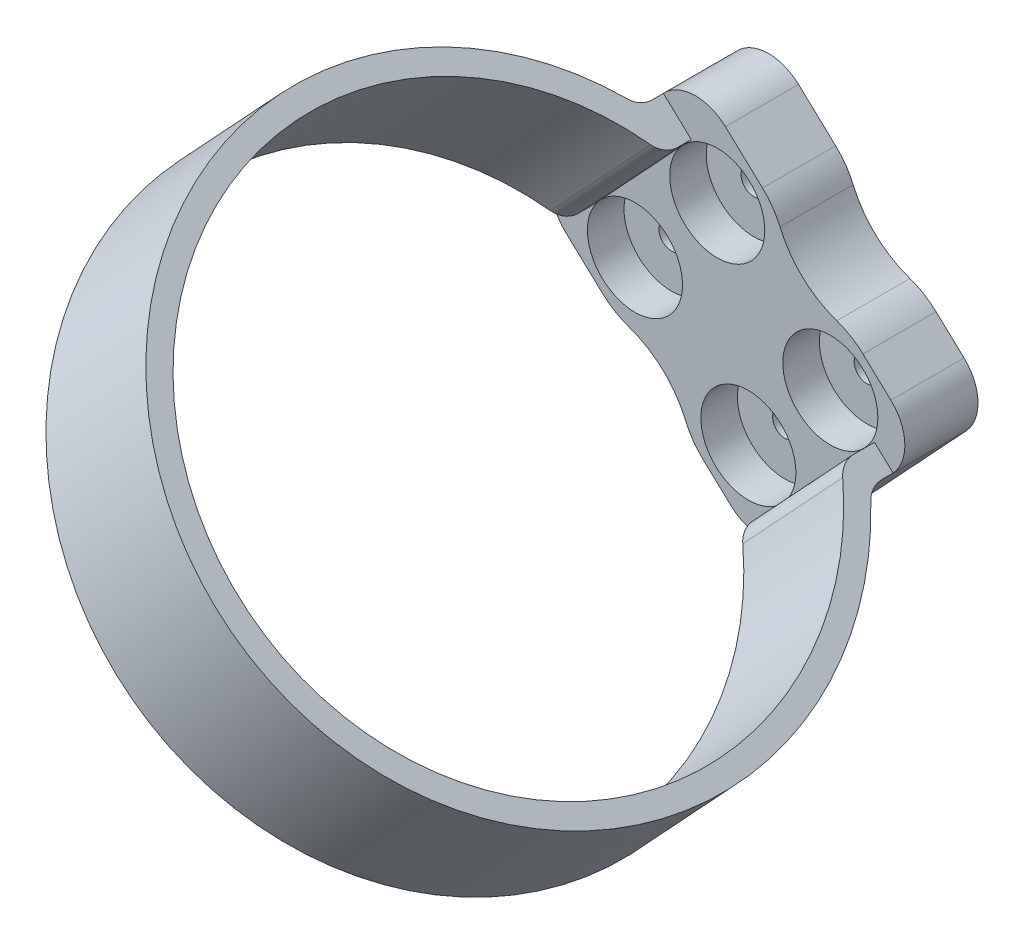
SolidWorks part; units mm, degrees
note: '?' marks a value the reader was unsure of.
ref_plane "Front Plane" through (0, 0, 0) normal (0, 0, 1) x (1, 0, 0)
ref_plane "Top Plane" through (0, 0, 0) normal (0, 1, 0) x (1, 0, 0)
ref_plane "Right Plane" through (0, 0, 0) normal (1, 0, 0) x (0, 0, -1)
sketch "Sketch1" plane through (0, 0, 0) normal (0, 0, 1) x (1, 0, 0)
  line L0 (-3.0751, 21.3626) -> (19.5471, 0.292)
  line L1 (10.5836, 36.0271) -> (33.2058, 14.9565)
  line L2 (19.5471, 0.292) -> (33.2058, 14.9565)
  line L3 (10.5836, 36.0271) -> (-3.0751, 21.3626)
extrude "Boss-Extrude2" add sketch "Sketch1" along normal blind 10
ref_plane "Plane2" through (22.8846, 24.5698, 0) normal (0.6816, 0.7318, 0) x (-0.7318, 0.6816, 0)
sketch "Sketch3" plane through (22.8846, 24.5698, 0) normal (0.6816, 0.7318, 0) x (-0.7318, 0.6816, 0)
  circle A0 centre (1.3528, 46.8926) radius 40
  circle A1 centre (1.3528, 46.8926) radius 37
  dimension "D1" = 80
  dimension "D2" = 3
extrude "Boss-Extrude3" add sketch "Sketch3" against normal up to vertex (20.0402 mm away)
sketch "Sketch5" plane through (0, 0, 0) normal (0, 0, -1) x (-1, 0, 0)
  circle A1 centre (-13.5527, 30.822) radius 1.747
  circle A2 centre (-2.3068, 18.748) radius 1.747
  circle A4 centre (-17.811, 4.2618) radius 1.6834
  circle A5 centre (-29.0179, 16.394) radius 1.747
extrude "Cut-Extrude1" cut sketch "Sketch5" against normal up to next
sketch "Sketch10" plane through (9.2259, 9.9053, 0) normal (-0.6816, -0.7318, 0) x (0.7318, -0.6816, 0)
  line L1 (14.1047, 10) -> (-16.8103, 10)
  line L2 (14.1047, 10) -> (14.1047, 0)
  line L3 (14.1047, 0) -> (-16.8103, 0)
  line L4 (-16.8103, 10) -> (-16.8103, 0)
extrude "Boss-Extrude8" add sketch "Sketch10" along normal blind 6
sketch "Sketch11" plane through (22.8846, 24.5698, 0) normal (0.6816, 0.7318, 0) x (0.7318, -0.6816, 0)
  line L1 (-16.8103, -10) -> (14.1047, -10)
  line L2 (-16.8103, -10) -> (-16.8103, 0)
  line L3 (-16.8103, 0) -> (14.1047, 0)
  line L4 (14.1047, -10) -> (14.1047, 0)
extrude "Boss-Extrude9" add sketch "Sketch11" along normal blind 6
sketch "Sketch12" plane through (-12.301, 11.4573, 0) normal (-0.7318, 0.6816, 0) x (0, 0, 1)
  line L1 (10, 39.5765) -> (0, 39.5765)
  line L2 (10, 39.5765) -> (10, 7.5363)
  line L3 (10, 7.5363) -> (0, 7.5363)
  line L4 (0, 39.5765) -> (0, 7.5363)
extrude "Boss-Extrude10" add sketch "Sketch12" along normal blind 6
sketch "Sketch13" plane through (10.3212, -9.6133, 0) normal (0.7318, -0.6816, 0) x (0, 0, -1)
  line L1 (0, 39.5765) -> (-10, 39.5765)
  line L2 (0, 39.5765) -> (0, 7.5363)
  line L3 (0, 7.5363) -> (-10, 7.5363)
  line L4 (-10, 39.5765) -> (-10, 7.5363)
extrude "Boss-Extrude11" add sketch "Sketch13" along normal blind 6
fillet "Fillet3" radius 6 4 edges at (41.6857, 15.2576, 5) (19.8482, -8.188, 5) (-11.5551, 21.0615, 5) (10.2824, 44.507, 5)
sketch "Sketch15" plane through (0, 0, 10) normal (0, 0, 1) x (1, 0, 0)
  line L0 (19.5471, 0.292) -> (23.9376, -3.7974)
  line L1 (19.5471, 0.292) -> (33.2058, 14.9565)
  line L2 (23.9376, -3.7974) -> (37.5963, 10.8671)
  line L3 (33.2058, 14.9565) -> (37.5963, 10.8671)
  line L4 (37.5963, 10.8671) -> (23.9376, -3.7974) construction
  dimension "D1" = 0
extrude "Boss-Extrude12" add sketch "Sketch15" along normal up to next
sketch "Sketch16" plane through (0, 0, 10) normal (0, 0, 1) x (1, 0, 0)
  line L0 (10.5836, 36.0271) -> (6.193, 40.1165)
  line L1 (10.5836, 36.0271) -> (-3.0751, 21.3626)
  line L2 (6.193, 40.1165) -> (-7.4657, 25.452)
  line L3 (-3.0751, 21.3626) -> (-7.4657, 25.452)
  dimension "D1" = 0
extrude "Boss-Extrude13" add sketch "Sketch16" along normal up to next
sketch "Sketch17" plane through (0, 0, 10) normal (0, 0, 1) x (1, 0, 0)
  circle A0 centre (2.3068, 18.748) radius 6.5
  circle A1 centre (13.5527, 30.822) radius 6.5
  circle A2 centre (17.811, 4.2618) radius 6.5
  circle A3 centre (29.0179, 16.394) radius 6.5
  dimension "D1" = 13
  dimension "D2" = 13
  dimension "D3" = 13
  dimension "D4" = 13
extrude "Cut-Extrude3" cut sketch "Sketch17" against normal blind 5 and the other way up to next
sketch "Sketch18" plane through (0, 0, 10) normal (0, 0, 1) x (1, 0, 0)
  line L0 (21.3939, -1.4282) -> (-3.6457, 21.894)
  line L1 (21.3939, -1.4282) -> (35.1886, 13.3823)
  line L2 (-3.6457, 21.894) -> (10.149, 36.7045)
  line L3 (35.1886, 13.3823) -> (10.149, 36.7045)
  circle A2 centre (17.811, 4.2618) radius 1.6834 construction
  circle A3 centre (2.3068, 18.748) radius 1.747 construction
  dimension "D1" = 6.5
  dimension "D2" = 6.5
extrude "Cut-Extrude4" cut sketch "Sketch18" along normal up to next
ref_point "Point1"
ref_axis "Axis1" through (21.8947, 25.4918, 46.8926) along (0.6816, 0.7318, 0)?
fillet "Fillet4" radius 3 4 edges at (3.1837, 29.2263, 13.6458) (28.2233, 5.9041, 14.5558) (-0.6363, 32.7842, 13.135) (30.767, 3.5348, 13.135)
sketch "Sketch19" plane through (0, 0, 0) normal (0, 0, -1) x (-1, 0, 0)
  line L0 (-29.0179, 16.394) -> (-13.5527, 30.822) construction
  line L1 (-21.2853, 23.608) -> (-34.1057, 37.35) construction
  line L3 (-37.2952, 19.347) -> (-14.673, 40.4176) construction
  line L4 (-31.6783, 24.5787) -> (-21.5388, 34.0228)
  line L5 (-2.3068, 18.748) -> (-17.811, 4.2618) construction
  line L6 (-10.0589, 11.5049) -> (2.734, -2.1869) construction
  line L7 (7.1645, 16.9721) -> (-15.4577, -4.0986) construction
  line L8 (0.3065, 10.5844) -> (-9.833, 1.1404)
  arc A0 (-31.6783, 24.5787) -> (-21.5388, 34.0228) centre (-34.1057, 37.35) ccw
  arc A1 (0.3065, 10.5844) -> (-9.833, 1.1404) centre (2.734, -2.1869) ccw
  dimension "D1" = 13
  dimension "D3" = 13
  dimension "D2" = 11
  dimension "D4" = 11
extrude "Cut-Extrude5" cut sketch "Sketch19" against normal up to next
fillet "Fillet5" radius 10 4 edges at (31.6783, 24.5787, 5) (21.5388, 34.0228, 5) (-0.3065, 10.5844, 5) (9.833, 1.1404, 5)
